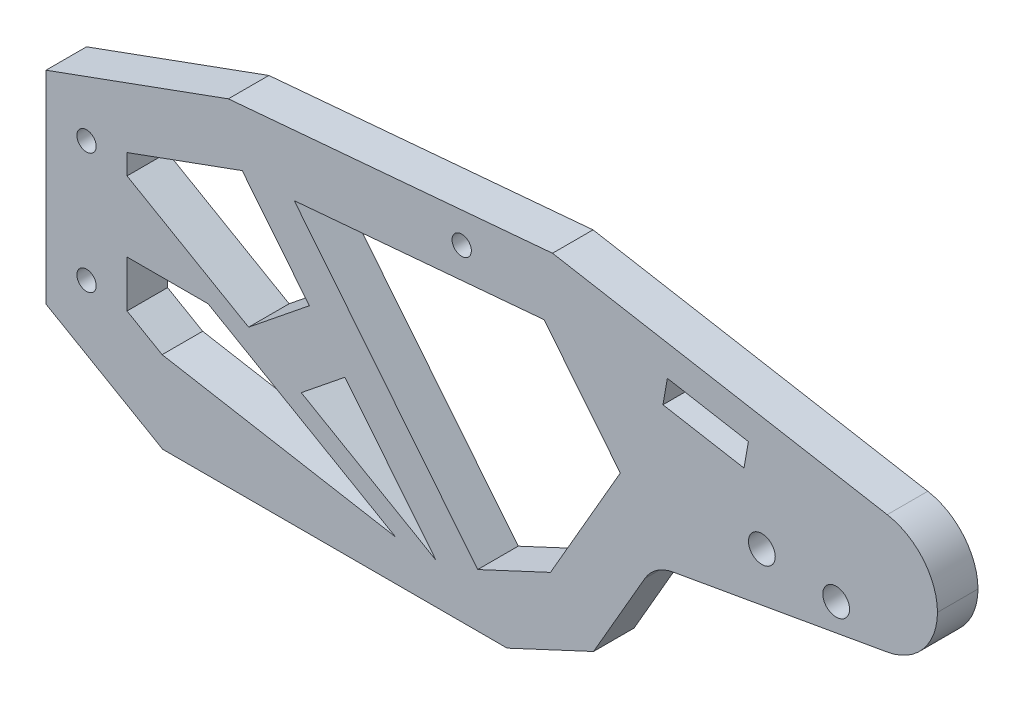
SolidWorks part; units mm, degrees
ref_plane "Plan de face" through (0, 0, 0) normal (0, 0, 1) x (1, 0, 0)
ref_plane "Plan de dessus" through (0, 0, 0) normal (0, 1, 0) x (1, 0, 0)
ref_plane "Plan de droite" through (0, 0, 0) normal (1, 0, 0) x (0, 0, -1)
sketch "Esquisse1" plane through (0, 0, 0) normal (0, 0, 1) x (1, 0, 0)
  line L1 (0, 0) -> (220, 0)
  line L2 (0, 0) -> (0, 90)
  line L3 (0, 90) -> (220, 90)
  line L4 (220, 0) -> (220, 90)
  dimension "D1" = 90
  dimension "D2" = 220
extrude "Boss.-Extru.1" add sketch "Esquisse1" along normal blind 10 contours L3 L4 L1 L2
sketch "Esquisse2" plane through (0, 0, 10) normal (0, 0, 1) x (1, 0, 0)
  line L0 (220, 73.2489) -> (125, 90)
  line L1 (220, 0) -> (220, 90) construction
  line L2 (0, 90) -> (220, 90) construction
  line L3 (125, 90) -> (45, 83.0009)
  line L4 (45, 83.0009) -> (0, 66.6222)
  line L5 (0, 0) -> (0, 90) construction
  line L6 (0, 66.6222) -> (0, 16.6222)
  line L7 (0, 16.6222) -> (28.7906, 0)
  line L8 (0, 0) -> (220, 0) construction
  line L9 (28.7906, 0) -> (113.7906, 0)
  line L10 (113.7906, 0) -> (135.1213, 9.9467)
  line L11 (135.1213, 9.9467) -> (150.1213, 35.9274)
  line L12 (150.1213, 35.9274) -> (220, 48.2489)
  line L13 (220, 48.2489) -> (220, 73.2489)
  dimension "D1" = 10
  dimension "D2" = 10
  dimension "D3" = 25
  dimension "D4" = 30
  dimension "D5" = 15
  dimension "D6" = 5
  dimension "D7" = 25
  dimension "D8" = 50
  dimension "D9" = 45
  dimension "D10" = 95
  dimension "D11" = 15
  dimension "D12" = 85
extrude "Enlèv. mat.-Extru.1" cut sketch "Esquisse2" against normal through all flip side to cut
sketch "Esquisse3" plane through (0, 0, 10) normal (0, 0, 1) x (1, 0, 0)
  line L0 (124.4956, 21.5425) -> (141.7327, 51.398)
  line L1 (141.7327, 51.398) -> (122.9121, 74.76)
  line L2 (122.9121, 74.76) -> (61.2631, 69.3664)
  line L3 (61.2631, 69.3664) -> (106.537, 13.1682)
  line L4 (96.248, 10) -> (73.7768, 37.8934)
  line L5 (73.7768, 37.8934) -> (62.9886, 29.2023)
  line L6 (62.9886, 29.2023) -> (96.248, 10)
  line L8 (20, 25.1543) -> (20, 36.7013)
  line L9 (20, 36.7013) -> (40, 36.7013)
  line L10 (40, 36.7013) -> (86.248, 10)
  line L11 (20, 54.0218) -> (49.9982, 36.7023)
  line L12 (49.9982, 36.7023) -> (65, 48.7879)
  line L13 (65, 48.7879) -> (48.4217, 69.3664)
  line L14 (48.4217, 69.3664) -> (20, 59.0218)
  line L15 (20, 59.0218) -> (20, 54.0218)
  line L16 (125, 90) -> (45, 83.0009) construction
  line L17 (135.1213, 9.9467) -> (150.1213, 35.9274) construction
  line L18 (0, 16.6222) -> (28.7906, 0) construction
  line L19 (113.7906, 0) -> (135.1213, 9.9467) construction
  line L20 (28.6603, 20.1543) -> (86.248, 10)
  line L21 (45, 83.0009) -> (0, 66.6222) construction
  line L22 (0, 16.6222) -> (0, 66.6222) construction
  line L23 (106.537, 13.1682) -> (124.4956, 21.5425)
  line L24 (28.7906, 0) -> (113.7906, 0) construction
  line L25 (20, 25.1543) -> (28.6603, 20.1543)
  dimension "D1" = 10
  dimension "D2" = 30
  dimension "D3" = 5
  dimension "D4" = 20
  dimension "D5" = 45
  dimension "D6" = 10
  dimension "D7" = 20
  dimension "D9" = 15
  dimension "D10" = 5
  dimension "D11" = 15
  dimension "D12" = 15
  dimension "D13" = 20
  dimension "D14" = 15
  dimension "D15" = 10
  dimension "D16" = 20
extrude "Enlèv. mat.-Extru.2" cut sketch "Esquisse3" against normal through all
fillet "Congé1" radius 15 2 edges at (220, 73.2489, 5) (220, 48.2489, 5)
sketch "Esquisse4" plane through (0, 0, 10) normal (0, 0, 1) x (1, 0, 0)
  line L0 (194.9998, 50.5372) -> (194.9998, 77.6572) construction
  line L1 (207.6047, 75.4346) -> (125, 90) construction
  circle A0 centre (194.9998, 50.5372) radius 3.305
  circle A1 centre (176.6617, 52.6212) radius 3.305
  point P8 (176.9773, 52.7427)
  dimension "D1" = 6.61
  dimension "D2" = 25
  dimension "D4" = 18.338
  dimension "D3" = 27.12
  dimension "D5" = 2.084
extrude "Enlèv. mat.-Extru.3" cut sketch "Esquisse4" against normal through all
hole_wizard "Perçage pour écrous auto-bloquants 300® #6 (SP)1" positions "Esquisse5" profile "Esquisse6" hole size "#6-32" standard "PEM® Inch" end condition through all
sketch "Esquisse5" plane through (0, 0, 10) normal (0, 0, 1) x (1, 0, 0)
  line L21 (102.9121, 73.0103) -> (102.5846, 80.5103) construction
  line L22 (102.5846, 80.5103) -> (102.2572, 88.0103) construction
  line L24 (122.9121, 74.76) -> (61.2631, 69.3664) construction
  line L25 (125, 90) -> (45, 83.0009) construction
  point P41 (102.5846, 80.5103)
  dimension "D1" = 7.5
  dimension "D2" = 20
sketch "Esquisse6" plane through (102.5846, 80.5103, 10) normal (1, 0, 0) x (0, -1, 0)
  line L0 (0, 0) -> (0, 10)
  line L1 (0, 10) -> (2.3812, 10)
  line L2 (2.3812, 10) -> (2.3812, 0)
  line L5 (2.3812, 0) -> (0, 0)
  line L11 (0, -6.35) -> (0, 107.95) construction
  dimension "Diamètre du perçage jusqu'au prochain" = 4.7625
  dimension "Profondeur du perçage jusqu'au prochain" = 10
hole_wizard "Perçage pour écrous auto-bloquants 300® #6 (SP)2" positions "Esquisse8" profile "Esquisse9" hole size "#6-32" standard "PEM® Inch" end condition through all
sketch "Esquisse8" plane through (0, 0, 10) normal (0, 0, 1) x (1, 0, 0)
  line L0 (10, 56.5218) -> (0, 56.5218) construction
  line L1 (0, 16.6222) -> (0, 66.6222) construction
  line L3 (10, 56.5218) -> (20, 56.5218) construction
  line L4 (20, 59.0218) -> (20, 54.0218) construction
  line L6 (10, 56.5218) -> (10, 26.7227) construction
  point P0 (10, 56.5218)
  point P2 (10, 26.7227)
  point P23 (0, 41.6222)
  point P24 (10, 41.6222)
  point P26 (20, 56.5218)
sketch "Esquisse9" plane through (10, 56.5218, 10) normal (1, 0, 0) x (0, -1, 0)
  line L0 (0, 0) -> (0, 10)
  line L1 (0, 10) -> (2.3812, 10)
  line L2 (2.3812, 10) -> (2.3812, 0)
  line L5 (2.3812, 0) -> (0, 0)
  line L11 (0, -6.35) -> (0, 107.95) construction
  dimension "Diamètre du perçage jusqu'au prochain" = 4.7625
  dimension "Profondeur du perçage jusqu'au prochain" = 10
sketch "Esquisse10" plane through (0, 0, 10) normal (0, 0, 1) x (1, 0, 0)
  line L0 (153.346, 77.4471) -> (152.252, 71.2428)
  line L1 (153.346, 77.4471) -> (173.3376, 73.922)
  line L2 (152.252, 71.2428) -> (172.2436, 67.7177)
  line L3 (173.3376, 73.922) -> (172.2436, 67.7177)
  line L4 (162.2478, 69.4802) -> (194.9998, 50.5372) construction
  line L6 (207.6047, 75.4346) -> (125, 90) construction
  dimension "D1" = 20.3
  dimension "D2" = 6.3
  dimension "D3" = 37.8355
  dimension "D4" = 7.44
extrude "Enlèv. mat.-Extru.4" cut sketch "Esquisse10" against normal blind 10 contours L1 L3 L2 L0
fillet "Congé2" radius 10 1 edges at (150.1213, 35.9274, 5)
